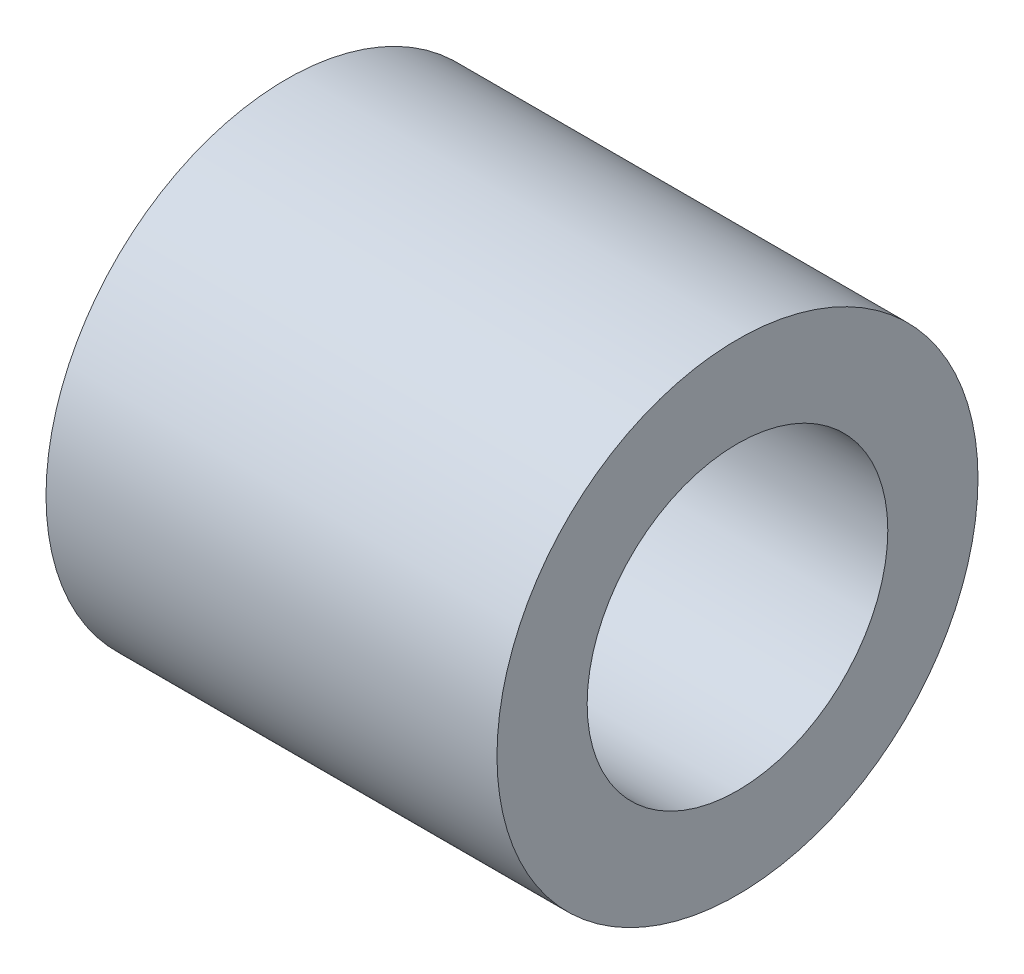
SolidWorks part; units mm, degrees
ref_plane "Front Plane" through (0, 0, 0) normal (0, 0, 1) x (1, 0, 0)
ref_plane "Top Plane" through (0, 0, 0) normal (0, 1, 0) x (1, 0, 0)
ref_plane "Right Plane" through (0, 0, 0) normal (1, 0, 0) x (0, 0, -1)
sketch "Sketch1" plane through (0, 0, 0) normal (1, 0, 0) x (0, 0, -1)
  circle A0 centre (0, 0) radius 5
  circle A1 centre (0, 0) radius 8
  dimension "D1" = 16
  dimension "D2" = 10
extrude "Boss-Extrude1" add sketch "Sketch1" along normal blind 15
